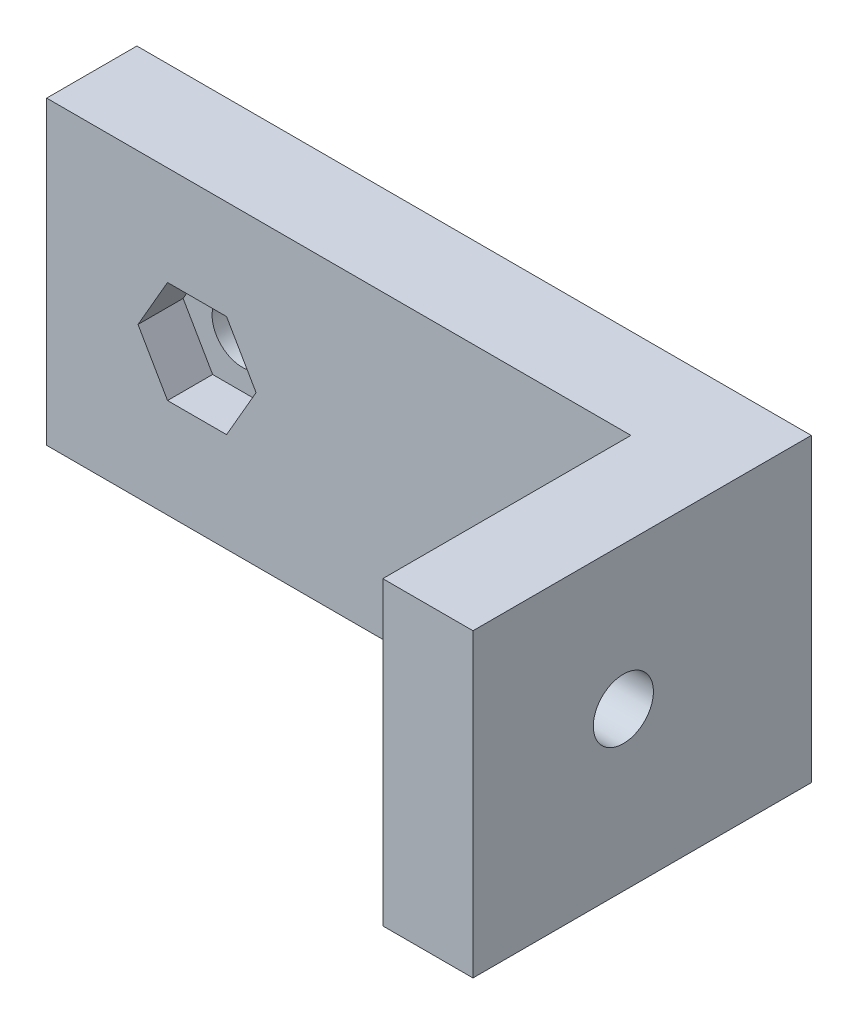
SolidWorks part; units mm, degrees
material "ABS"
ref_plane "Front Plane" through (0, 0, 0) normal (0, 0, 1) x (1, 0, 0)
ref_plane "Top Plane" through (0, 0, 0) normal (0, 1, 0) x (1, 0, 0)
ref_plane "Right Plane" through (0, 0, 0) normal (1, 0, 0) x (0, 0, -1)
sketch "Sketch1" plane through (0, 0, 0) normal (0, 0, 1) x (1, 0, 0)
  line L0 (169.7, 145.6824) -> (169.7, -24.5) construction
  line L1 (169.7, -7.5) -> (124.85, -7.5)
  line L2 (169.7, -7.5) -> (169.7, 12.5)
  line L3 (169.7, 12.5) -> (124.85, 12.5)
  line L4 (124.85, -7.5) -> (124.85, 12.5)
  line L5 (169.7, -7.5) -> (124.85, 12.5) construction
  line L6 (169.7, 12.5) -> (124.85, -7.5) construction
  line L8 (130.924, 2.5) -> (132.887, -0.9)
  line L9 (132.887, -0.9) -> (136.813, -0.9)
  line L10 (136.813, -0.9) -> (138.776, 2.5)
  line L11 (138.776, 2.5) -> (136.813, 5.9)
  line L12 (136.813, 5.9) -> (132.887, 5.9)
  line L13 (132.887, 5.9) -> (130.924, 2.5)
  circle A0 centre (134.85, 2.5) radius 2
  circle A1 centre (134.85, 2.5) radius 3.4 construction
  point P4 (147.275, 2.5)
  point P10 (134.85, 5.9)
  dimension "D2" = 10
  dimension "D3" = 10
  dimension "D4" = 10
  dimension "D1" = 6.8
extrude "Boss-Extrude1" add sketch "Sketch1" along normal blind 3 contours L4 L1 L2 L3 L13 L12 L11 L10 L9 L8 | L12 L13 L8 L9 L10 L11 A0 region at (147.8556, 2.5, 0) region at (131.9955, 4.1481, 0)
extrude "Boss-Extrude2" add sketch "Sketch1<4>" along normal blind 3 from surface contours L4 L1 L2 L3 L13 L12 L11 L10 L9 L8 region at (147.8556, 2.5, 0) starting at face at (147.275, 2.5, 3)
sketch "Sketch1<4>" plane through (0, 0, 0) normal (0, 0, 1) x (1, 0, 0) same geometry as "Sketch1"
sketch "Sketch5" plane through (169.7, 0, 0) normal (-1, 0, 0) x (0, 0, 1)
  line L0 (6, 12.5) -> (0, 12.5) construction
  line L1 (6, -7.5) -> (22.5, -7.5)
  line L2 (6, -7.5) -> (6, 12.5)
  line L3 (6, 12.5) -> (22.5, 12.5)
  line L4 (22.5, -7.5) -> (22.5, 12.5)
  line L5 (6, -7.5) -> (22.5, 12.5) construction
  line L6 (6, 12.5) -> (22.5, -7.5) construction
  line L8 (12.5, -0.926) -> (15.9, 1.037)
  line L9 (15.9, 1.037) -> (15.9, 4.963)
  line L10 (15.9, 4.963) -> (12.5, 6.926)
  line L11 (12.5, 6.926) -> (9.1, 4.963)
  line L12 (9.1, 4.963) -> (9.1, 1.037)
  line L13 (9.1, 1.037) -> (12.5, -0.926)
  circle A0 centre (12.5, 3) radius 2
  circle A1 centre (12.5, 3) radius 3.4 construction
  point P7 (14.25, 2.5)
  circle M18 centre (12.5, 3) radius 2
  dimension "D1" = 10
  dimension "D2" = 6.8
extrude "Boss-Extrude3" add sketch "Sketch5" along normal blind 3 contours L1 L4 L3 L2 L13 L12 L11 L10 L9 L8 | L12 L13 L8 L9 L10 L11 M18 region at (169.7, 2.5, 6.2593) region at (169.7, 0.1455, 10.8519)
extrude "Boss-Extrude4" add sketch "Sketch5<3>" along normal blind 3 from surface contours L1 L4 L3 L2 L13 L12 L11 L10 L9 L8 region at (169.7, 2.5, 6.2593) starting at face at (166.7, 2.5, 14.25)
sketch "Sketch5<3>" plane through (169.7, 0, 0) normal (-1, 0, 0) x (0, 0, 1) same geometry as "Sketch5"
